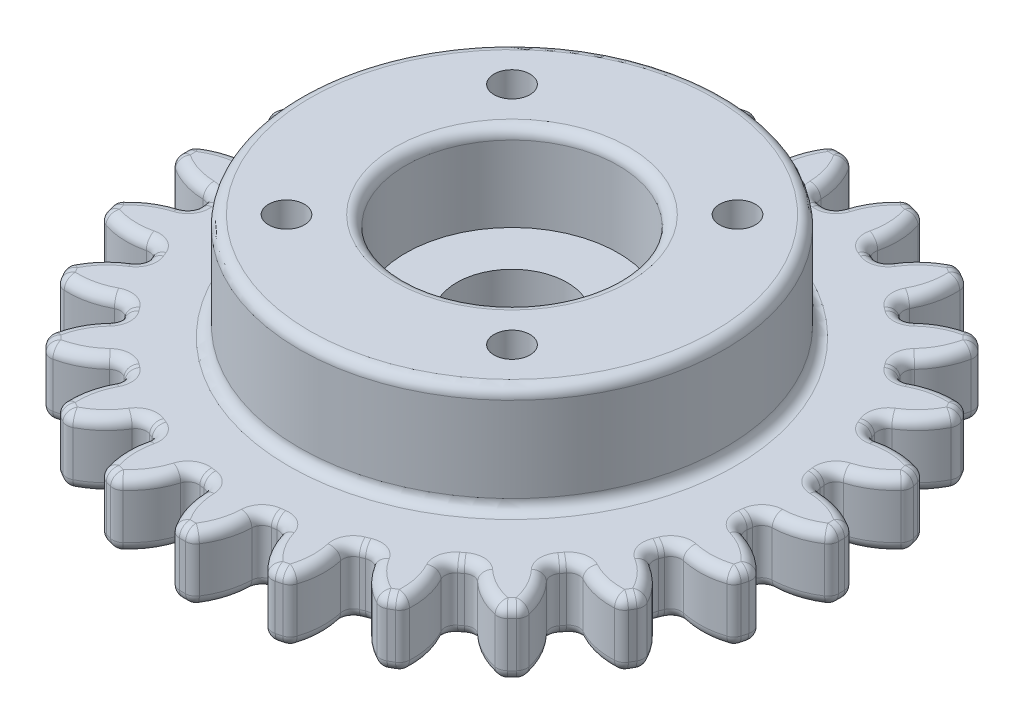
SolidWorks part; units mm, degrees
ref_plane "Front Plane" through (0, 0, 0) normal (0, 0, 1) x (1, 0, 0)
ref_plane "Top Plane" through (0, 0, 0) normal (0, 1, 0) x (1, 0, 0)
ref_plane "Right Plane" through (0, 0, 0) normal (1, 0, 0) x (0, 0, -1)
sketch "Sketch2" plane through (0, 0, 0) normal (0, 1, 0) x (1, 0, 0)
  line L0 (1.6066, 22.8619) -> (0, 0) construction
  line L1 (1.6066, 22.8619) -> (6.4656, 5.8944) construction
  line L2 (-1.8126, 20.7187) -> (0, 0) construction
  line L3 (0, 0) -> (1.8126, 20.7187) construction
  line L4 (-3.6115, 20.4818) -> (0, 0) construction
  line L5 (-6.4181, 23.9528) -> (0, 0) construction
  circle A0 centre (0, 0) radius 20.7978 construction
  circle A1 centre (0, 0) radius 24.7978 construction
  arc A2 (1.8126, 20.7187) -> (0.6469, 24.7894) centre (-4.078, 21.234) ccw
  arc A3 (-1.8126, 20.7187) -> (-0.6469, 24.7894) centre (4.078, 21.234) cw
  arc A4 (0.6469, 24.7894) -> (-0.6469, 24.7894) centre (0, 0) ccw
  arc A5 (1.8126, 20.7187) -> (3.6115, 20.4818) centre (0, 0) cw
  arc A6 (3.6115, 20.4818) -> (5.7911, 24.1121) centre (9.4348, 19.455) cw
  arc A7 (7.0408, 23.7772) -> (5.7911, 24.1121) centre (0, 0) ccw
  arc A8 (7.1133, 19.5435) -> (7.0408, 23.7772) centre (1.5567, 21.566) ccw
  arc A9 (7.1133, 19.5435) -> (8.7895, 18.8492) centre (0, 0) cw
  arc A10 (8.7895, 18.8492) -> (11.8344, 21.7917) centre (14.1487, 16.3502) cw
  arc A11 (12.9549, 21.1447) -> (11.8344, 21.7917) centre (0, 0) ccw
  arc A12 (11.9291, 17.0366) -> (12.9549, 21.1447) centre (7.0854, 20.4282) ccw
  arc A13 (11.9291, 17.0366) -> (13.3686, 15.932) centre (0, 0) cw
  arc A14 (13.3686, 15.932) -> (17.0713, 17.9862) centre (17.8983, 12.1311) cw
  arc A15 (17.9862, 17.0713) -> (17.0713, 17.9862) centre (0, 0) ccw
  arc A16 (15.932, 13.3686) -> (17.9862, 17.0713) centre (12.1311, 17.8983) ccw
  arc A17 (15.932, 13.3686) -> (17.0366, 11.9291) centre (0, 0) cw
  arc A18 (17.0366, 11.9291) -> (21.1447, 12.9549) centre (20.4282, 7.0854) cw
  arc A19 (21.7917, 11.8344) -> (21.1447, 12.9549) centre (0, 0) ccw
  arc A20 (18.8492, 8.7895) -> (21.7917, 11.8344) centre (16.3502, 14.1487) ccw
  arc A21 (18.8492, 8.7895) -> (19.5435, 7.1133) centre (0, 0) cw
  arc A22 (19.5435, 7.1133) -> (23.7772, 7.0408) centre (21.566, 1.5567) cw
  arc A23 (24.1121, 5.7911) -> (23.7772, 7.0408) centre (0, 0) ccw
  arc A24 (20.4818, 3.6115) -> (24.1121, 5.7911) centre (19.455, 9.4348) ccw
  arc A25 (20.4818, 3.6115) -> (20.7187, 1.8126) centre (0, 0) cw
  arc A26 (20.7187, 1.8126) -> (24.7894, 0.6469) centre (21.234, -4.078) cw
  arc A27 (24.7894, -0.6469) -> (24.7894, 0.6469) centre (0, 0) ccw
  arc A28 (20.7187, -1.8126) -> (24.7894, -0.6469) centre (21.234, 4.078) ccw
  arc A29 (20.7187, -1.8126) -> (20.4818, -3.6115) centre (0, 0) cw
  arc A30 (20.4818, -3.6115) -> (24.1121, -5.7911) centre (19.455, -9.4348) cw
  arc A31 (23.7772, -7.0408) -> (24.1121, -5.7911) centre (0, 0) ccw
  arc A32 (19.5435, -7.1133) -> (23.7772, -7.0408) centre (21.566, -1.5567) ccw
  arc A33 (19.5435, -7.1133) -> (18.8492, -8.7895) centre (0, 0) cw
  arc A34 (18.8492, -8.7895) -> (21.7917, -11.8344) centre (16.3502, -14.1487) cw
  arc A35 (21.1447, -12.9549) -> (21.7917, -11.8344) centre (0, 0) ccw
  arc A36 (17.0366, -11.9291) -> (21.1447, -12.9549) centre (20.4282, -7.0854) ccw
  arc A37 (17.0366, -11.9291) -> (15.932, -13.3686) centre (0, 0) cw
  arc A38 (15.932, -13.3686) -> (17.9862, -17.0713) centre (12.1311, -17.8983) cw
  arc A39 (17.0713, -17.9862) -> (17.9862, -17.0713) centre (0, 0) ccw
  arc A40 (13.3686, -15.932) -> (17.0713, -17.9862) centre (17.8983, -12.1311) ccw
  arc A41 (13.3686, -15.932) -> (11.9291, -17.0366) centre (0, 0) cw
  arc A42 (11.9291, -17.0366) -> (12.9549, -21.1447) centre (7.0854, -20.4282) cw
  arc A43 (11.8344, -21.7917) -> (12.9549, -21.1447) centre (0, 0) ccw
  arc A44 (8.7895, -18.8492) -> (11.8344, -21.7917) centre (14.1487, -16.3502) ccw
  arc A45 (8.7895, -18.8492) -> (7.1133, -19.5435) centre (0, 0) cw
  arc A46 (7.1133, -19.5435) -> (7.0408, -23.7772) centre (1.5567, -21.566) cw
  arc A47 (5.7911, -24.1121) -> (7.0408, -23.7772) centre (0, 0) ccw
  arc A48 (3.6115, -20.4818) -> (5.7911, -24.1121) centre (9.4348, -19.455) ccw
  arc A49 (3.6115, -20.4818) -> (1.8126, -20.7187) centre (0, 0) cw
  arc A50 (1.8126, -20.7187) -> (0.6469, -24.7894) centre (-4.078, -21.234) cw
  arc A51 (-0.6469, -24.7894) -> (0.6469, -24.7894) centre (0, 0) ccw
  arc A52 (-1.8126, -20.7187) -> (-0.6469, -24.7894) centre (4.078, -21.234) ccw
  arc A53 (-1.8126, -20.7187) -> (-3.6115, -20.4818) centre (0, 0) cw
  arc A54 (-3.6115, -20.4818) -> (-5.7911, -24.1121) centre (-9.4348, -19.455) cw
  arc A55 (-7.0408, -23.7772) -> (-5.7911, -24.1121) centre (0, 0) ccw
  arc A56 (-7.1133, -19.5435) -> (-7.0408, -23.7772) centre (-1.5567, -21.566) ccw
  arc A57 (-7.1133, -19.5435) -> (-8.7895, -18.8492) centre (0, 0) cw
  arc A58 (-8.7895, -18.8492) -> (-11.8344, -21.7917) centre (-14.1487, -16.3502) cw
  arc A59 (-12.9549, -21.1447) -> (-11.8344, -21.7917) centre (0, 0) ccw
  arc A60 (-11.9291, -17.0366) -> (-12.9549, -21.1447) centre (-7.0854, -20.4282) ccw
  arc A61 (-11.9291, -17.0366) -> (-13.3686, -15.932) centre (0, 0) cw
  arc A62 (-13.3686, -15.932) -> (-17.0713, -17.9862) centre (-17.8983, -12.1311) cw
  arc A63 (-17.9862, -17.0713) -> (-17.0713, -17.9862) centre (0, 0) ccw
  arc A64 (-15.932, -13.3686) -> (-17.9862, -17.0713) centre (-12.1311, -17.8983) ccw
  arc A65 (-15.932, -13.3686) -> (-17.0366, -11.9291) centre (0, 0) cw
  arc A66 (-17.0366, -11.9291) -> (-21.1447, -12.9549) centre (-20.4282, -7.0854) cw
  arc A67 (-21.7917, -11.8344) -> (-21.1447, -12.9549) centre (0, 0) ccw
  arc A68 (-18.8492, -8.7895) -> (-21.7917, -11.8344) centre (-16.3502, -14.1487) ccw
  arc A69 (-18.8492, -8.7895) -> (-19.5435, -7.1133) centre (0, 0) cw
  arc A70 (-19.5435, -7.1133) -> (-23.7772, -7.0408) centre (-21.566, -1.5567) cw
  arc A71 (-24.1121, -5.7911) -> (-23.7772, -7.0408) centre (0, 0) ccw
  arc A72 (-20.4818, -3.6115) -> (-24.1121, -5.7911) centre (-19.455, -9.4348) ccw
  arc A73 (-20.4818, -3.6115) -> (-20.7187, -1.8126) centre (0, 0) cw
  arc A74 (-20.7187, -1.8126) -> (-24.7894, -0.6469) centre (-21.234, 4.078) cw
  arc A75 (-24.7894, 0.6469) -> (-24.7894, -0.6469) centre (0, 0) ccw
  arc A76 (-20.7187, 1.8126) -> (-24.7894, 0.6469) centre (-21.234, -4.078) ccw
  arc A77 (-20.7187, 1.8126) -> (-20.4818, 3.6115) centre (0, 0) cw
  arc A78 (-20.4818, 3.6115) -> (-24.1121, 5.7911) centre (-19.455, 9.4348) cw
  arc A79 (-23.7772, 7.0408) -> (-24.1121, 5.7911) centre (0, 0) ccw
  arc A80 (-19.5435, 7.1133) -> (-23.7772, 7.0408) centre (-21.566, 1.5567) ccw
  arc A81 (-19.5435, 7.1133) -> (-18.8492, 8.7895) centre (0, 0) cw
  arc A82 (-18.8492, 8.7895) -> (-21.7917, 11.8344) centre (-16.3502, 14.1487) cw
  arc A83 (-21.1447, 12.9549) -> (-21.7917, 11.8344) centre (0, 0) ccw
  arc A84 (-17.0366, 11.9291) -> (-21.1447, 12.9549) centre (-20.4282, 7.0854) ccw
  arc A85 (-17.0366, 11.9291) -> (-15.932, 13.3686) centre (0, 0) cw
  arc A86 (-15.932, 13.3686) -> (-17.9862, 17.0713) centre (-12.1311, 17.8983) cw
  arc A87 (-17.0713, 17.9862) -> (-17.9862, 17.0713) centre (0, 0) ccw
  arc A88 (-13.3686, 15.932) -> (-17.0713, 17.9862) centre (-17.8983, 12.1311) ccw
  arc A89 (-13.3686, 15.932) -> (-11.9291, 17.0366) centre (0, 0) cw
  arc A90 (-11.9291, 17.0366) -> (-12.9549, 21.1447) centre (-7.0854, 20.4282) cw
  arc A91 (-11.8344, 21.7917) -> (-12.9549, 21.1447) centre (0, 0) ccw
  arc A92 (-8.7895, 18.8492) -> (-11.8344, 21.7917) centre (-14.1487, 16.3502) ccw
  arc A93 (-8.7895, 18.8492) -> (-7.1133, 19.5435) centre (0, 0) cw
  arc A94 (-7.1133, 19.5435) -> (-7.0408, 23.7772) centre (-1.5567, 21.566) cw
  arc A95 (-5.7911, 24.1121) -> (-7.0408, 23.7772) centre (0, 0) ccw
  arc A96 (-3.6115, 20.4818) -> (-5.7911, 24.1121) centre (-9.4348, 19.455) ccw
  arc A97 (-3.6115, 20.4818) -> (-1.8126, 20.7187) centre (0, 0) cw
  arc A98 (7.469, 21.6671) -> (1.6066, 22.8619) centre (0, 0) ccw construction
  arc A99 (-3.2334, 18.3373) -> (-4.8193, 17.9857) centre (0, 0) ccw
  arc A100 (-1.6229, 18.5494) -> (-3.2334, 18.3373) centre (0, 0) ccw
  point P12 (0, 24.7978)
  point P180 (0, 0)
  dimension "D2" = 4
  dimension "D1" = 20
  dimension "D4" = 6
  dimension "D3" = 24
extrude "Boss-Extrude1" add sketch "Sketch2" along normal blind 5 contours A8 A98 A6 A5 A2 A4 A3 A97 A96 A95 A94 A93 A92 A91 A90 A89 A88 A87 A86 A85 A84 A83 A82 A81 A80 A79 A78 A77 A76 A75 A74 A73 A72 A71 A70 A69 A68 A67 A66 A65 A64 A63 A62 A61 A60 A59 A58 A57 A56 A55 region at (0, 0, 0)
sketch "Sketch3" plane through (0, 5, 0) normal (0, 1, 0) x (1, 0, 0)
  circle A0 centre (0, 0) radius 4.15
  dimension "D1" = 8.3
extrude "Cut-Extrude1" cut sketch "Sketch3" against normal through all
sketch "Sketch4" plane through (0, 5, 0) normal (0, 1, 0) x (1, 0, 0)
  circle A0 centre (0, 0) radius 8
  circle A1 centre (0, 0) radius 16
  dimension "D1" = 16
  dimension "D2" = 8
extrude "Boss-Extrude2" add sketch "Sketch4" along normal blind 8
sketch "Sketch5" plane through (0, 13, 0) normal (0, 1, 0) x (1, 0, 0)
  line L1 (-8.4853, -8.4853) -> (8.4853, -8.4853) construction
  line L2 (-8.4853, -8.4853) -> (-8.4853, 8.4853) construction
  line L3 (-8.4853, 8.4853) -> (8.4853, 8.4853) construction
  line L4 (8.4853, -8.4853) -> (8.4853, 8.4853) construction
  line L5 (-8.4853, -8.4853) -> (8.4853, 8.4853) construction
  line L6 (-8.4853, 8.4853) -> (8.4853, -8.4853) construction
  circle A0 centre (8.4853, 8.4853) radius 1.35
  circle A1 centre (-8.4853, 8.4853) radius 1.35
  circle A2 centre (-8.4853, -8.4853) radius 1.35
  circle A3 centre (8.4853, -8.4853) radius 1.35
  point P0 (0, 0)
  dimension "D2" = 2.7
  dimension "D1" = 24
extrude "Cut-Extrude2" cut sketch "Sketch5" against normal blind 6
sketch "Sketch6" plane through (0, 5, 0) normal (0, 1, 0) x (1, 0, 0)
  circle A0 centre (0, 0) radius 4.15 construction
  circle A1 centre (0, 0) radius 4.15
  circle A2 centre (0, 0) radius 8 construction
  circle A3 centre (0, 0) radius 8
extrude "Boss-Extrude3" add sketch "Sketch6" along normal blind 1.5
fillet "Fillet2" radius 0.8 291 edges at (-3.6115, 2.5, -20.4818) (-5.7911, 2.5, -24.1121) (-7.0408, 2.5, -23.7772) (-7.1133, 2.5, -19.5435) (-8.7895, 2.5, -18.8492) (-11.8344, 2.5, -21.7917) (-12.9549, 2.5, -21.1447) (-11.9291, 2.5, -17.0366) (-13.3686, 2.5, -15.932) (-17.0713, 2.5, -17.9862) (-17.9862, 2.5, -17.0713) (-15.932, 2.5, -13.3686) (-17.0366, 2.5, -11.9291) (-21.1447, 2.5, -12.9549) (-21.7917, 2.5, -11.8344) (-18.8492, 2.5, -8.7895) (-19.5435, 2.5, -7.1133) (-23.7772, 2.5, -7.0408) (-24.1121, 2.5, -5.7911) (-20.4818, 2.5, -3.6115) (-20.7187, 2.5, -1.8126) (-24.7894, 2.5, -0.6469) (-24.7894, 2.5, 0.6469) (-20.7187, 2.5, 1.8126) (-20.4818, 2.5, 3.6115) (-24.1121, 2.5, 5.7911) (-23.7772, 2.5, 7.0408) (-19.5435, 2.5, 7.1133) (-18.8492, 2.5, 8.7895) (-21.7917, 2.5, 11.8344) (-21.1447, 2.5, 12.9549) (-17.0366, 2.5, 11.9291) (-15.932, 2.5, 13.3686) (-17.9862, 2.5, 17.0713) (-17.0713, 2.5, 17.9862) (-13.3686, 2.5, 15.932) (-11.9291, 2.5, 17.0366) (-12.9549, 2.5, 21.1447) (-11.8344, 2.5, 21.7917) (-8.7895, 2.5, 18.8492) (-7.1133, 2.5, 19.5435) (-7.0408, 2.5, 23.7772) (-5.7911, 2.5, 24.1121) (-3.6115, 2.5, 20.4818) (-1.8126, 2.5, 20.7187) (-0.6469, 2.5, 24.7894) (0.6469, 2.5, 24.7894) (1.8126, 2.5, 20.7187) (3.6115, 2.5, 20.4818) (5.7911, 2.5, 24.1121) (7.0408, 2.5, 23.7772) (7.1133, 2.5, 19.5435) (8.7895, 2.5, 18.8492) (11.8344, 2.5, 21.7917) (12.9549, 2.5, 21.1447) (11.9291, 2.5, 17.0366) (13.3686, 2.5, 15.932) (17.0713, 2.5, 17.9862) (17.9862, 2.5, 17.0713) (15.932, 2.5, 13.3686) (17.0366, 2.5, 11.9291) (21.1447, 2.5, 12.9549) (21.7917, 2.5, 11.8344) (18.8492, 2.5, 8.7895) (19.5435, 2.5, 7.1133) (23.7772, 2.5, 7.0408) (24.1121, 2.5, 5.7911) (20.4818, 2.5, 3.6115) (20.7187, 2.5, 1.8126) (24.7894, 2.5, 0.6469) (24.7894, 2.5, -0.6469) (20.7187, 2.5, -1.8126) (20.4818, 2.5, -3.6115) (24.1121, 2.5, -5.7911) (23.7772, 2.5, -7.0408) (19.5435, 2.5, -7.1133) (18.8492, 2.5, -8.7895) (21.7917, 2.5, -11.8344) (21.1447, 2.5, -12.9549) (17.0366, 2.5, -11.9291) (15.932, 2.5, -13.3686) (17.9862, 2.5, -17.0713) (17.0713, 2.5, -17.9862) (13.3686, 2.5, -15.932) (11.9291, 2.5, -17.0366) (12.9549, 2.5, -21.1447) (11.8344, 2.5, -21.7917) (8.7895, 2.5, -18.8492) (7.1133, 2.5, -19.5435) (7.0408, 2.5, -23.7772) (5.7911, 2.5, -24.1121) (3.6115, 2.5, -20.4818) (1.8126, 2.5, -20.7187) (0.6469, 2.5, -24.7894) (-0.6469, 2.5, -24.7894) (-1.8126, 2.5, -20.7187) (-1.6066, 5, -22.8619) (0, 5, -24.7978) (1.6066, 5, -22.8619) (2.7147, 5, -20.6199) (4.3652, 5, -22.4988) (6.4181, 5, -23.9528) (7.469, 5, -21.6671) (7.959, 5, -19.2147) (10.0396, 5, -20.6023) (12.3989, 5, -21.4755) (12.8224, 5, -18.9957) (12.6609, 5, -16.5) (15.0298, 5, -17.3019) (17.5347, 5, -17.5347) (17.3019, 5, -15.0298) (16.5, 5, -12.6609) (18.9957, 5, -12.8224) (21.4755, 5, -12.3989) (20.6023, 5, -10.0396) (19.2147, 5, -7.959) (21.6671, 5, -7.469) (23.9528, 5, -6.4181) (22.4988, 5, -4.3652) (20.6199, 5, -2.7147) (22.8619, 5, -1.6066) (24.7978, 5, 0) (22.8619, 5, 1.6066) (20.6199, 5, 2.7147) (22.4988, 5, 4.3652) (23.9528, 5, 6.4181) (21.6671, 5, 7.469) (19.2147, 5, 7.959) (20.6023, 5, 10.0396) (21.4755, 5, 12.3989) (18.9957, 5, 12.8224) (16.5, 5, 12.6609) (17.3019, 5, 15.0298) (17.5347, 5, 17.5347) (15.0298, 5, 17.3019) (12.6609, 5, 16.5) (12.8224, 5, 18.9957) (12.3989, 5, 21.4755) (10.0396, 5, 20.6023) (7.959, 5, 19.2147) (7.469, 5, 21.6671) (6.4181, 5, 23.9528) (4.3652, 5, 22.4988) (2.7147, 5, 20.6199) (1.6066, 5, 22.8619) (0, 5, 24.7978) (-1.6066, 5, 22.8619) (-2.7147, 5, 20.6199) (-4.3652, 5, 22.4988) (-6.4181, 5, 23.9528) (-7.469, 5, 21.6671) (-7.959, 5, 19.2147) (-10.0396, 5, 20.6023) (-12.3989, 5, 21.4755) (-12.8224, 5, 18.9957) (-12.6609, 5, 16.5) (-15.0298, 5, 17.3019) (-17.5347, 5, 17.5347) (-17.3019, 5, 15.0298) (-16.5, 5, 12.6609) (-18.9957, 5, 12.8224) (-21.4755, 5, 12.3989) (-20.6023, 5, 10.0396) (-19.2147, 5, 7.959) (-21.6671, 5, 7.469) (-23.9528, 5, 6.4181) (-22.4988, 5, 4.3652) (-20.6199, 5, 2.7147) (-22.8619, 5, 1.6066) (-24.7978, 5, 0) (-22.8619, 5, -1.6066) (-20.6199, 5, -2.7147) (-22.4988, 5, -4.3652) (-23.9528, 5, -6.4181) (-21.6671, 5, -7.469) (-19.2147, 5, -7.959) (-20.6023, 5, -10.0396) (-21.4755, 5, -12.3989) (-18.9957, 5, -12.8224) (-16.5, 5, -12.6609) (-17.3019, 5, -15.0298) (-17.5347, 5, -17.5347) (-15.0298, 5, -17.3019) (-12.6609, 5, -16.5) (-12.8224, 5, -18.9957) (-12.3989, 5, -21.4755) (-10.0396, 5, -20.6023) (-7.959, 5, -19.2147) (-7.469, 5, -21.6671) (-6.4181, 5, -23.9528) (-4.3652, 5, -22.4988) (-2.7147, 5, -20.6199) (-1.6066, 0, -22.8619) (0, 0, -24.7978) (1.6066, 0, -22.8619) (2.7147, 0, -20.6199) (4.3652, 0, -22.4988) (6.4181, 0, -23.9528) (7.469, 0, -21.6671) (7.959, 0, -19.2147) (10.0396, 0, -20.6023) (12.3989, 0, -21.4755) (12.8224, 0, -18.9957) (12.6609, 0, -16.5) (15.0298, 0, -17.3019) (17.5347, 0, -17.5347) (17.3019, 0, -15.0298) (16.5, 0, -12.6609) (18.9957, 0, -12.8224) (21.4755, 0, -12.3989) (20.6023, 0, -10.0396) (19.2147, 0, -7.959) (21.6671, 0, -7.469) (23.9528, 0, -6.4181) (22.4988, 0, -4.3652) (20.6199, 0, -2.7147) (22.8619, 0, -1.6066) (24.7978, 0, 0) (22.8619, 0, 1.6066) (20.6199, 0, 2.7147) (22.4988, 0, 4.3652) (23.9528, 0, 6.4181) (21.6671, 0, 7.469) (19.2147, 0, 7.959) (20.6023, 0, 10.0396) (21.4755, 0, 12.3989) (18.9957, 0, 12.8224) (16.5, 0, 12.6609) (17.3019, 0, 15.0298) (17.5347, 0, 17.5347) (15.0298, 0, 17.3019) (12.6609, 0, 16.5) (12.8224, 0, 18.9957) (12.3989, 0, 21.4755) (10.0396, 0, 20.6023) (7.959, 0, 19.2147) (7.469, 0, 21.6671) (6.4181, 0, 23.9528) (4.3652, 0, 22.4988) (2.7147, 0, 20.6199) (1.6066, 0, 22.8619) (0, 0, 24.7978) (-1.6066, 0, 22.8619) (-2.7147, 0, 20.6199) (-4.3652, 0, 22.4988) (-6.4181, 0, 23.9528) (-7.469, 0, 21.6671) (-7.959, 0, 19.2147) (-10.0396, 0, 20.6023) (-12.3989, 0, 21.4755) (-12.8224, 0, 18.9957) (-12.6609, 0, 16.5) (-15.0298, 0, 17.3019) (-17.5347, 0, 17.5347) (-17.3019, 0, 15.0298) (-16.5, 0, 12.6609) (-18.9957, 0, 12.8224) (-21.4755, 0, 12.3989) (-20.6023, 0, 10.0396) (-19.2147, 0, 7.959) (-21.6671, 0, 7.469) (-23.9528, 0, 6.4181) (-22.4988, 0, 4.3652) (-20.6199, 0, 2.7147) (-22.8619, 0, 1.6066) (-24.7978, 0, 0) (-22.8619, 0, -1.6066) (-20.6199, 0, -2.7147) (-22.4988, 0, -4.3652) (-23.9528, 0, -6.4181) (-21.6671, 0, -7.469) (-19.2147, 0, -7.959) (-20.6023, 0, -10.0396) (-21.4755, 0, -12.3989) (-18.9957, 0, -12.8224) (-16.5, 0, -12.6609) (-17.3019, 0, -15.0298) (-17.5347, 0, -17.5347) (-15.0298, 0, -17.3019) (-12.6609, 0, -16.5) (-12.8224, 0, -18.9957) (-12.3989, 0, -21.4755) (-10.0396, 0, -20.6023) (-7.959, 0, -19.2147) (-7.469, 0, -21.6671) (-6.4181, 0, -23.9528) (-4.3652, 0, -22.4988) (-2.7147, 0, -20.6199) (0, 13, 8) (0, 5, 16) (0, 13, 16)
